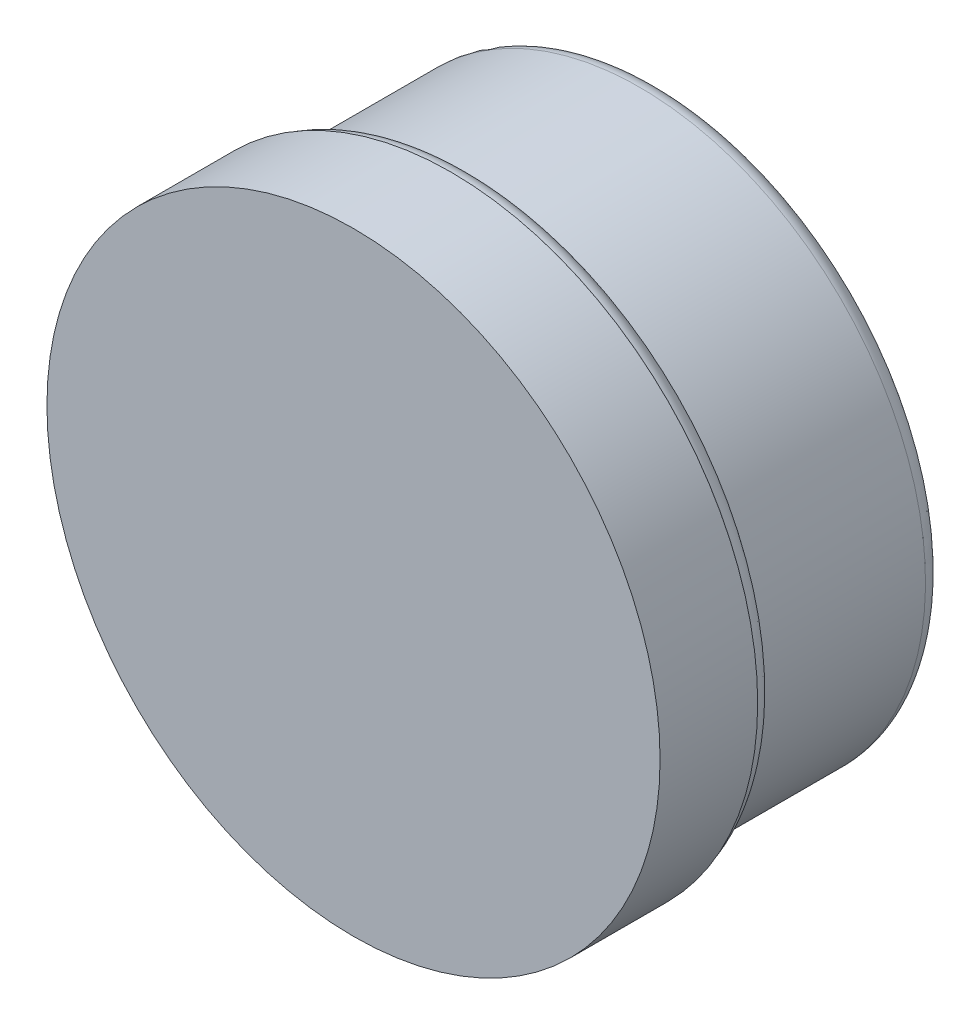
SolidWorks part; units mm, degrees
ref_plane "Front Plane" through (0, 0, 0) normal (1, 0, 0) x (0, 1, 0)
ref_plane "Top Plane" through (0, 0, 0) normal (0, 0, 1) x (0, 1, 0)
ref_plane "Right Plane" through (0, 0, 0) normal (0, 1, 0) x (-1, 0, 0)
ref_axis "x axis" through (-88.99, 0, 0) along (1, 0, 0)
ref_axis "y xxis" through (0, 88.99, 0) along (0, -1, 0)
ref_axis "z axis" through (0, 0, 55) along (0, 0, -1)
sketch "Sketch4" plane through (0, 0, 0) normal (1, 0, 0) x (0, 1, 0)
  line L0 (0, 0) -> (30.55, 0)
  line L1 (32.65, 2.1) -> (32.65, 21.5)
  line L2 (32.65, 21.5) -> (32.85, 21.5)
  line L3 (34.85, 23.5) -> (34.85, 23.55)
  line L4 (34.85, 23.55) -> (32.65, 23.55)
  line L5 (32.65, 23.55) -> (32.65, 26.5)
  line L6 (32.65, 26.5) -> (33.25, 26.5)
  line L7 (33.25, 26.5) -> (33.25, 27.7)
  line L8 (33.25, 27.7) -> (32.65, 27.7)
  line L9 (32.65, 27.7) -> (32.65, 29)
  line L10 (32.65, 29) -> (31.15, 29)
  line L11 (31.15, 29) -> (31.15, 3)
  line L12 (29.65, 1.5) -> (0, 1.5)
  line L13 (0, 1.5) -> (0, 0)
  arc A0 (30.55, 0) -> (32.65, 2.1) centre (30.55, 2.1) ccw
  arc A1 (31.15, 3) -> (29.65, 1.5) centre (29.65, 3) cw
  arc A2 (32.85, 21.5) -> (34.85, 23.5) centre (32.85, 23.5) ccw
  point P17 (32.65, 0)
  point P20 (0, 0)
  point P23 (34.85, 21.5)
  dimension "D4" = 2.1
  dimension "D5" = 1.5
  dimension "D12" = 2
  dimension "D1" = 32.65
  dimension "D2" = 29
  dimension "D3" = 1.5
  dimension "D6" = 2.2
  dimension "D7" = 0.6
  dimension "D8" = 21.5
  dimension "D9" = 1.3
  dimension "D10" = 1.2
  dimension "D11" = 2.05
revolve "Revolve1" add sketch "Sketch4" angle 360 about L13
sketch "Sketch6" plane through (0, 0, 0) normal (1, 0, 0) x (0, 1, 0)
  line L0 (0, 33.3) -> (0, 34.8)
  line L1 (0, 34.8) -> (35.025, 34.8)
  line L2 (35.025, 34.8) -> (35.025, 23.65)
  line L3 (35.025, 23.65) -> (33.275, 23.65)
  line L4 (33.275, 23.65) -> (33.275, 25.05)
  line L5 (33.275, 25.05) -> (32.775, 25.05)
  line L6 (32.775, 25.05) -> (32.775, 26.05)
  line L7 (32.775, 26.05) -> (33.275, 26.05)
  line L8 (33.275, 26.05) -> (33.275, 33.3)
  line L9 (33.275, 33.3) -> (0, 33.3)
  line L10 (34.85, 23.55) -> (-34.85, 23.55) construction
  point P9 (0, 0)
  dimension "D1" = 35.025
  dimension "D2" = 1.5
  dimension "D3" = 1.75
  dimension "D4" = 11.15
  dimension "D5" = 0.5
  dimension "D6" = 1.4
  dimension "D7" = 1
  dimension "D8" = 0.1
revolve "Revolve2" add sketch "Sketch6" angle 360 about L0
sketch "Sketch7" plane through (0, 0, 23.65) normal (0, 0, -1) x (1, 0, 0)
  line L0 (0, 35.025) -> (0, 0) construction
  line L1 (0, 35.025) -> (0, 37.525) construction
  arc A0 (9.85, 33.6114) -> (-9.85, 33.6114) centre (0, 0) ccw
  circle A1 centre (0, 0) radius 35.025 construction
  arc A2 (-8, 36.6623) -> (8, 36.6623) centre (0, 0) cw
  arc A3 (-9.85, 33.6114) -> (-8, 36.6623) centre (-7.427, 34.2285) cw
  arc A4 (8, 36.6623) -> (9.85, 33.6114) centre (7.427, 34.2285) cw
  point P12 (-8, 36.6623)
  point P13 (0, 0)
  point P14 (0, 0)
  dimension "D1" = 19.7
  dimension "D2" = 16
  dimension "D3" = 2.5
extrude "Boss-Extrude3" add sketch "Sketch7" against normal blind 1.6
